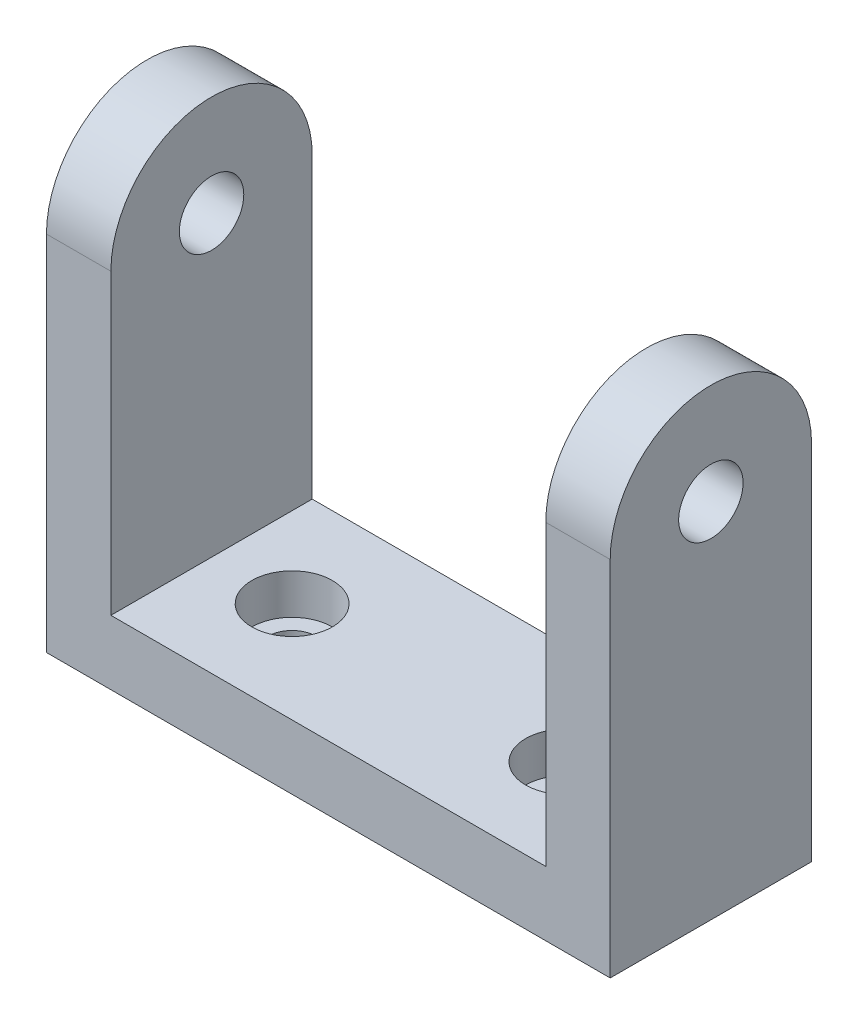
SolidWorks part; units mm, degrees
ref_plane "Front Plane" through (0, 0, 0) normal (0, 0, 1) x (1, 0, 0)
ref_plane "Top Plane" through (0, 0, 0) normal (0, 1, 0) x (1, 0, 0)
ref_plane "Right Plane" through (0, 0, 0) normal (1, 0, 0) x (0, 0, -1)
sketch "Sketch1" plane through (0, 0, 0) normal (0, 1, 0) x (1, 0, 0)
  line L1 (-26.954, 14.3391) -> (43.046, 14.3391)
  line L2 (-26.954, 14.3391) -> (-26.954, -10.6609)
  line L3 (-26.954, -10.6609) -> (43.046, -10.6609)
  line L4 (43.046, 14.3391) -> (43.046, -10.6609)
  dimension "D1" = 70
  dimension "D2" = 25
extrude "Boss-Extrude1" add sketch "Sketch1" along normal blind 8
sketch "Sketch2" plane through (0, 8, 0) normal (0, 1, 0) x (1, 0, 0)
  line L0 (43.046, -10.6609) -> (43.046, 14.3391) construction
  circle A0 centre (25.046, 1.8391) radius 5
  circle A1 centre (25.046, 1.8391) radius 3
  point P5 (0, 0)
  point P10 (0, 0)
  point P11 (0, 0)
  point P12 (43.046, 1.8391)
  dimension "D1" = 10
  dimension "D2" = 6
  dimension "D3" = 18
extrude "Cut-Extrude1" cut sketch "Sketch2" against normal through all contours A1
extrude "Cut-Extrude2" cut sketch "Sketch2<3>" against normal blind 5 contours A0
sketch "Sketch2<3>" plane through (0, 8, 0) normal (0, 1, 0) x (1, 0, 0) same geometry as "Sketch2"
sketch "Sketch3" plane through (43.046, 0, 0) normal (1, 0, 0) x (0, 0, -1)
  line L0 (-10.6609, 45) -> (-10.6609, 8)
  line L2 (-10.6609, 8) -> (14.3391, 8)
  line L3 (14.3391, 8) -> (14.3391, 45)
  arc A0 (14.3391, 45) -> (-10.6609, 45) centre (1.8391, 45) ccw
  circle A1 centre (1.8391, 45) radius 4
  point P14 (1.8391, 8)
  dimension "D2" = 25
  dimension "D1" = 8
extrude "Boss-Extrude2" add sketch "Sketch3" against normal blind 8
ref_plane "Plane1" through (8.046, 0, 0) normal (1, 0, 0) x (0, 0, -1)
mirror "Mirror1" about plane through (8.046, 0, 0) normal (1, 0, 0) of "Cut-Extrude1", "Cut-Extrude2", "Boss-Extrude2"
